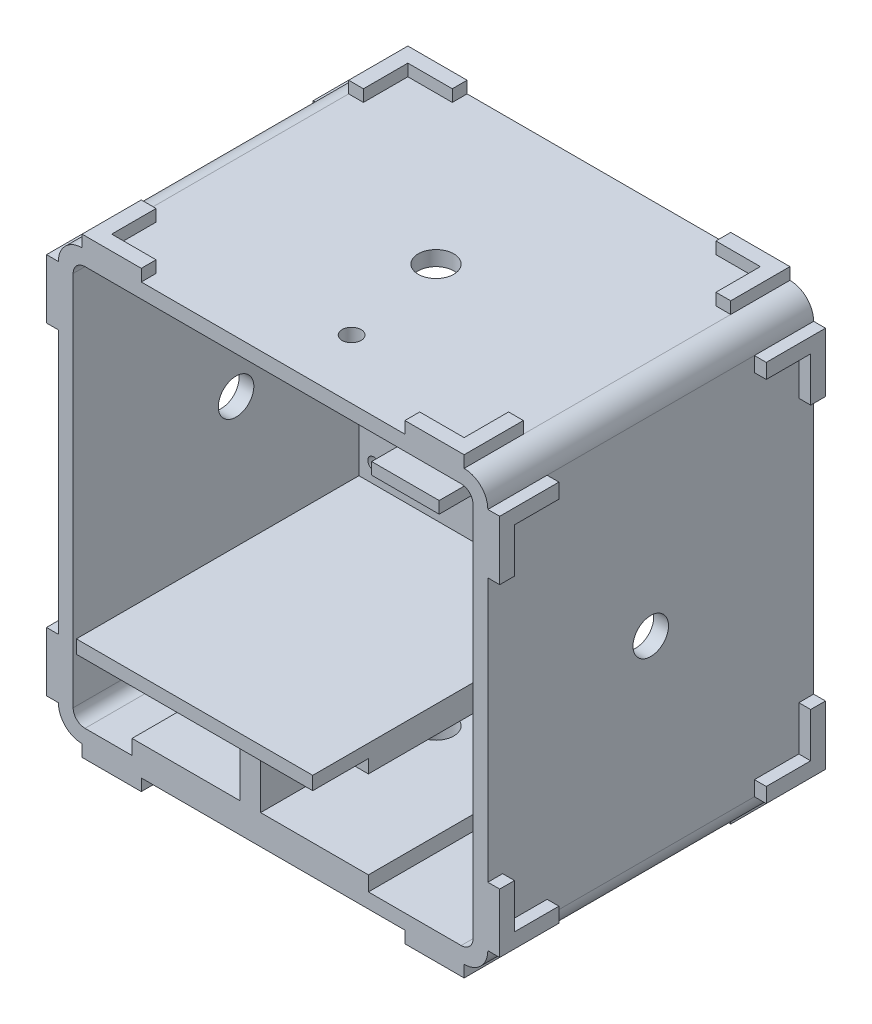
SolidWorks part; units mm, degrees
ref_plane "Front Plane" through (0, 0, 0) normal (0, 0, 1) x (1, 0, 0)
ref_plane "Top Plane" through (0, 0, 0) normal (0, 1, 0) x (1, 0, 0)
ref_plane "Right Plane" through (0, 0, 0) normal (1, 0, 0) x (0, 0, -1)
sketch "Sketch1" plane through (0, 0, 0) normal (0, 0, 1) x (1, 0, 0)
  line L0 (-33.75, -33.75) -> (33.75, -33.75) construction
  line L1 (-31.75, 33.75) -> (31.75, 33.75)
  line L2 (-33.75, 31.75) -> (-33.75, -31.75)
  line L3 (-31.75, -33.75) -> (31.75, -33.75)
  line L4 (33.75, 31.75) -> (33.75, -31.75)
  line L5 (-36.25, 32.25) -> (-36.25, -32.25)
  line L6 (33.75, 33.75) -> (33.75, -33.75) construction
  line L7 (-32.25, -36.25) -> (32.25, -36.25)
  line L8 (36.25, 32.25) -> (36.25, -32.25)
  line L9 (-32.25, 36.25) -> (32.25, 36.25)
  line L10 (-36.25, 36.25) -> (-36.25, -36.25) construction
  line L11 (-36.25, 36.25) -> (36.25, 36.25) construction
  line L12 (-33.75, 33.75) -> (33.75, 33.75) construction
  line L13 (-33.75, 33.75) -> (-33.75, -33.75) construction
  line L14 (-36.25, -36.25) -> (36.25, -36.25) construction
  line L15 (36.25, 36.25) -> (36.25, -36.25) construction
  line L16 (55, 0) -> (-55, 0) construction
  line L17 (0, -55) -> (0, 55) construction
  arc A0 (-36.25, 32.25) -> (-32.25, 36.25) centre (-32.25, 32.25) cw
  arc A1 (-31.75, 33.75) -> (-33.75, 31.75) centre (-31.75, 31.75) ccw
  arc A2 (-33.75, -31.75) -> (-31.75, -33.75) centre (-31.75, -31.75) ccw
  arc A3 (31.75, -33.75) -> (33.75, -31.75) centre (31.75, -31.75) ccw
  arc A4 (31.75, 33.75) -> (33.75, 31.75) centre (31.75, 31.75) cw
  arc A5 (-36.25, -32.25) -> (-32.25, -36.25) centre (-32.25, -32.25) ccw
  arc A6 (32.25, -36.25) -> (36.25, -32.25) centre (32.25, -32.25) ccw
  arc A7 (36.25, 32.25) -> (32.25, 36.25) centre (32.25, 32.25) ccw
  point P36 (-33.75, 0)
  point P39 (0, 33.75)
  dimension "D3" = 4
  dimension "D4" = 2
  dimension "D5" = 2
  dimension "D6" = 4
  dimension "D1" = 67.5
  dimension "D2" = 2.5
extrude "Boss-Extrude1" add sketch "Sketch1" along normal blind 55
sketch "Sketch2" plane through (0, 0, 0) normal (0, 0, 1) x (1, 0, 0)
  line L1 (-33.75, 33.75) -> (33.75, 33.75)
  line L2 (-33.75, 33.75) -> (-33.75, -33.75)
  line L3 (-33.75, -33.75) -> (33.75, -33.75)
  line L4 (33.75, 33.75) -> (33.75, -33.75)
extrude "Boss-Extrude2" add sketch "Sketch2" along normal blind 2.5
sketch "Sketch3" plane through (0, 0, 2.5) normal (0, 0, 1) x (1, 0, 0)
  line L0 (-4.38, 17.29) -> (-18.88, 12.29) construction
  line L1 (-19.88, 11.29) -> (-3.38, 11.29)
  line L2 (-18.88, 12.29) -> (-4.38, 12.29) construction
  line L3 (-18.88, 12.29) -> (-18.88, 17.29) construction
  line L4 (-18.88, 17.29) -> (-4.38, 17.29) construction
  line L5 (-4.38, 12.29) -> (-4.38, 17.29) construction
  line L6 (-3.38, 11.29) -> (-3.38, 18.29)
  line L7 (-19.88, 18.29) -> (-3.38, 18.29)
  line L8 (-19.88, 11.29) -> (-19.88, 18.29)
  line L9 (-36.25, 32.25) -> (-36.25, -32.25) construction
  line L10 (-3, -7) -> (3, -7) construction
  line L11 (-3, -7) -> (-3, 7) construction
  line L12 (-3, 7) -> (3, 7) construction
  line L13 (3, -7) -> (3, 7) construction
  line L14 (-3, -7) -> (3, 7) construction
  line L15 (-3, 7) -> (3, -7) construction
  line L16 (32.25, 36.25) -> (-32.25, 36.25) construction
  line L17 (-4, -8) -> (-4, 8)
  line L18 (-4, 8) -> (4, 8)
  line L19 (4, -8) -> (4, 8)
  line L20 (-4, -8) -> (4, -8)
  line L21 (-18.88, 17.29) -> (-4.38, 12.29) construction
  point P0 (0, 0)
  dimension "D2" = 6
  dimension "D3" = 14
  dimension "D5" = 14.5
  dimension "D6" = 5
  dimension "D7" = 16.37
  dimension "D8" = 23.96
  dimension "D1" = 1
  dimension "D4" = 1
extrude "Cut-Extrude1" cut sketch "Sketch3" against normal up to next
fillet "Fillet1" radius 1 8 edges at (-19.88, 11.29, 1.25) (-19.88, 18.29, 1.25) (-3.38, 18.29, 1.25) (-3.38, 11.29, 1.25) (4, -8, 1.25) (-4, -8, 1.25) (-4, 8, 1.25) (4, 8, 1.25)
sketch "Sketch4" plane through (0, 0, 0) normal (0, 0, -1) x (-1, 0, 0)
  line L0 (-32.25, 36.25) -> (32.25, 36.25) construction
  line L1 (-36.25, -32.25) -> (-36.25, 32.25) construction
  circle A0 centre (-28.75, 28.75) radius 1.5
  dimension "D3" = 3
  dimension "D1" = 7.5
  dimension "D2" = 7.5
extrude "Cut-Extrude2" cut sketch "Sketch4" against normal up to next
mirror "Mirror1" about plane through (0, 0, 0) normal (1, 0, 0) of "Cut-Extrude2"
mirror "Mirror2" about plane through (0, 0, 0) normal (0, 1, 0) of "Mirror1"
sketch "Sketch5" plane through (0, 0, 0) normal (1, 0, 0) x (0, 0, -1)
  line L0 (-14.7, 14) -> (-64.4, 14)
  line L1 (-16.7, 12) -> (-62.4, 12)
  line L2 (-16.7, 12) -> (-16.7, -12)
  line L3 (-16.7, -12) -> (-62.4, -12)
  line L5 (-64.4, 14) -> (-64.4, 12)
  line L6 (-14.7, -14) -> (-64.4, -14)
  line L7 (-14.7, 14) -> (-14.7, -14)
  line L8 (-62.4, 12) -> (-64.4, 12)
  line L9 (-62.4, -12) -> (-64.4, -12)
  line L10 (-64.4, -12) -> (-64.4, -14)
  line L11 (-62.4, 12) -> (-62.4, -12) construction
  line L12 (-64.4, 14) -> (-64.4, -14) construction
  line L13 (30.25, 0) -> (-30.25, 0) construction
  line L14 (-55, 32.25) -> (-55, -32.25) construction
  point P4 (0, 0)
  point P6 (0, 0)
  point P11 (0, 0)
  point P13 (0, 0)
  point P14 (0, 0)
  point P15 (0, 0)
  point P18 (0, 0)
  point P19 (-64.3967, 12)
  point P20 (0, 0)
  point P21 (-64.3967, -14)
  point P22 (-64.3967, -12)
  point P23 (-62.3967, -12)
  point P24 (-17.3967, 14)
  dimension "D1" = 45.7
  dimension "D2" = 24
  dimension "D4" = 12
  dimension "D5" = 9.4
  dimension "D3" = 2
extrude "Boss-Extrude3" add sketch "Sketch5" along normal blind 16.09 and the other way blind 23.81 separate body
sketch "Sketch6" plane through (0, 0, 64.4) normal (0, 0, 1) x (1, 0, 0)
  line L0 (-23.81, -14) -> (16.09, -14) construction
  line L1 (-23.81, -14) -> (16.09, -14)
  line L2 (-23.81, -14) -> (-23.81, -16.5)
  line L3 (-23.81, -16.5) -> (-5.61, -16.5)
  line L4 (16.09, -14) -> (16.09, -16.5)
  line L5 (-31.75, -33.75) -> (31.75, -33.75) construction
  line L6 (-23.81, -33.75) -> (16.09, -33.75)
  line L7 (-23.81, -33.75) -> (-23.81, -31.25)
  line L8 (-23.81, -31.25) -> (-5.61, -31.25)
  line L9 (16.09, -33.75) -> (16.09, -31.25)
  line L10 (-2.11, -16.5) -> (16.09, -16.5)
  line L12 (-5.61, -16.5) -> (-5.61, -31.25)
  line L14 (-2.11, -16.5) -> (-2.11, -31.25)
  line L15 (-2.11, -31.25) -> (16.09, -31.25)
  line L16 (-23.81, -12) -> (-23.81, -14) construction
  point P16 (0, 0)
  point P17 (0, 0)
  point P20 (0, 0)
  point P21 (0, 0)
  point P22 (0, 0)
  point P23 (5.59, -33.75)
  point P24 (-23.81, -33.75)
  point P25 (0, 0)
  point P26 (0, 0)
  point P27 (0, 0)
  point P28 (0, 0)
  point P29 (-23.81, -14)
  point P30 (-23.81, -16.5)
  point P31 (0, 0)
  dimension "D1" = 2.5
  dimension "D2" = 2.5
  dimension "D3" = 39.9
  dimension "D4" = 39.9
  dimension "D5" = 3.5
  dimension "D6" = 18.2
  dimension "D7" = 18.2
extrude "Boss-Extrude4" add sketch "Sketch6" against normal blind 47
sketch "Sketch7" plane through (0, 0, 64.4) normal (0, 0, 1) x (1, 0, 0)
  line L0 (-23.81, -12) -> (-23.81, -16.5) construction
  line L1 (-23.81, -14.25) -> (16.09, -14.25)
  line L2 (-23.81, -14.25) -> (-23.81, -33.75)
  line L3 (-23.81, -33.75) -> (16.09, -33.75)
  line L4 (16.09, -14.25) -> (16.09, -33.75)
  line L5 (16.09, -33.75) -> (31.75, -33.75) construction
  line L6 (16.09, -33.75) -> (16.09, -31.25) construction
extrude "Cut-Extrude3" cut sketch "Sketch7" against normal blind 9.4
sketch "Sketch8" plane through (-23.81, 0, 0) normal (-1, 0, 0) x (0, 0, 1)
  line L0 (16.7, 12) -> (16.7, -12) construction
  line L1 (16.7, 12) -> (22.2, 12)
  line L2 (16.7, 12) -> (16.7, 6.5)
  line L3 (16.7, 6.5) -> (20.6, 6.5)
  line L4 (22.2, 12) -> (22.2, 8.1)
  arc A0 (20.6, 6.5) -> (22.2, 8.1) centre (20.6, 8.1) ccw
  circle A1 centre (19.7, 9) radius 1 construction
  circle A2 centre (19.7, 9) radius 1.8
  dimension "D1" = 1.6
  dimension "D4" = 3.6
  dimension "D5" = 2
  dimension "D2" = 5.5
  dimension "D3" = 5.5
  dimension "D6" = 3
  dimension "D7" = 3
extrude "Boss-Extrude5" [suppressed] add sketch "Sketch8" against normal blind 3
sketch "Sketch9" [suppressed] plane through (-15.56, 0, 0) normal (-1, 0, 0) x (0, 0, 1)
  circle A0 centre (22.3967, 9) radius 1
  circle A1 centre (22.3967, 9) radius 2
  dimension "D1" = 2
  dimension "D2" = 1
extrude "Boss-Extrude6" [suppressed] add sketch "Sketch9" along normal blind 1.5
ref_plane "Plane1" through (-9.11, 0, 0) normal (-1, 0, 0) x (0, 0, 1)
mirror "Mirror3" [suppressed] about plane through (-9.11, 0, 0) normal (-1, 0, 0)
ref_plane "Plane2" through (0, 0, 0) normal (0, 1, 0) x (1, 0, 0)
mirror "Mirror4" [suppressed] about plane through (0, 0, 0) normal (0, 1, 0)
sketch "Sketch10" [suppressed] plane through (-36.25, 0, 0) normal (-1, 0, 0) x (0, 0, 1)
  circle A0 centre (22.3967, 9) radius 1.5
  circle A1 centre (22.3967, -9) radius 1.5
  dimension "D1" = 3
  dimension "D2" = 3
extrude "Cut-Extrude4" [suppressed] cut sketch "Sketch10" against normal through all
sketch "Sketch12" plane through (0, 36.25, 0) normal (0, 1, 0) x (1, 0, 0)
  line L0 (-32.25, -55) -> (-32.25, 0) construction
  line L1 (32.25, -55) -> (29.75, -55)
  line L2 (32.25, -55) -> (32.25, -45)
  line L3 (32.25, -45) -> (29.75, -45)
  line L4 (29.75, -52.5) -> (29.75, -45)
  line L5 (32.25, -55) -> (22.25, -55)
  line L6 (32.25, -55) -> (32.25, -52.5)
  line L7 (29.75, -52.5) -> (22.25, -52.5)
  line L8 (22.25, -55) -> (22.25, -52.5)
  line L10 (-32.25, 0) -> (-32.25, -10)
  line L11 (-32.25, -10) -> (-29.75, -10)
  line L12 (-29.75, -2.5) -> (-29.75, -10)
  line L13 (-32.25, 0) -> (-22.25, 0)
  line L15 (-29.75, -2.5) -> (-22.25, -2.5)
  line L16 (-22.25, 0) -> (-22.25, -2.5)
  line M6 (-32.25, -55) -> (32.25, -55)
  line M7 (32.25, -55) -> (32.25, 0)
  dimension "D1" = 2.5
  dimension "D2" = 10
  dimension "D3" = 2.5
  dimension "D4" = 10
  dimension "D5" = 2.5
extrude "Boss-Extrude7" add sketch "Sketch12" along normal blind 2 contours L8 L2 L3 L4 L7 M6 M7 | L10 L11 L12 L15 L16 L13 region at (31, 36.25, 54.8586)
sketch "Sketch13" plane through (0, 0, 0) normal (0, 0, -1) x (-1, 0, 0)
  line L3 (-33.75, 21.25) -> (-25.25, 21.25)
  line L4 (-21.25, 33.75) -> (-21.25, 25.25)
  line L6 (0, 35.42) -> (0, -35.42) construction
  line L8 (21.25, 33.75) -> (21.25, 25.25)
  line L9 (33.75, 21.25) -> (25.25, 21.25)
  line L12 (35.42, 0) -> (-35.42, 0) construction
  line L17 (33.75, -21.25) -> (25.25, -21.25)
  line L18 (21.25, -33.75) -> (21.25, -25.25)
  line L19 (-21.25, -33.75) -> (-21.25, -25.25)
  line L20 (-33.75, -21.25) -> (-25.25, -21.25)
  line L27 (-33.75, 21.25) -> (-33.75, -21.25)
  line L29 (33.75, 21.25) -> (33.75, -21.25)
  line L34 (-21.25, 33.75) -> (21.25, 33.75)
  line L36 (-21.25, -33.75) -> (21.25, -33.75)
  arc A2 (-25.25, 21.25) -> (-21.25, 25.25) centre (-25.25, 25.25) ccw
  arc A4 (25.25, 21.25) -> (21.25, 25.25) centre (25.25, 25.25) cw
  arc A7 (25.25, -21.25) -> (21.25, -25.25) centre (25.25, -25.25) ccw
  arc A8 (-25.25, -21.25) -> (-21.25, -25.25) centre (-25.25, -25.25) cw
  dimension "D3" = 4
extrude "Cut-Extrude6" cut sketch "Sketch13" against normal up to next and the other way through all
sketch "Sketch14" plane through (0, 0, 14.7) normal (0, 0, -1) x (-1, 0, 0)
  line L1 (23.81, 14) -> (9.11, 14)
  line L2 (23.81, 14) -> (23.81, 12)
  line L3 (23.81, 12) -> (9.11, 12)
  line L4 (9.11, 14) -> (9.11, 12)
  dimension "D1" = 14.7
  dimension "D2" = 2
extrude "Cut-Extrude7" cut sketch "Sketch14" against normal up to next
sketch "Sketch15" plane through (0, 36.25, 0) normal (0, 1, 0) x (1, 0, 0)
  line L0 (22.25, -55) -> (-32.25, -55) construction
  line L1 (33.75, -55) -> (33.75, -2.5) construction
  circle A0 centre (3.25, -45) radius 1.6
  dimension "D1" = 3.2
  dimension "D2" = 10
  dimension "D3" = 30.5
extrude "Cut-Extrude8" cut sketch "Sketch15" against normal up to surface (2.5 mm away) and the other way through all up to face at (0, 33.75, 15)
sketch "Sketch16" plane through (-33.75, 0, 0) normal (1, 0, 0) x (0, 0, -1)
  line L2 (-16, 32.15) -> (-16, 29.65)
  line L7 (-16, 29.65) -> (-8.5, 29.65)
  line L9 (-16, 32.15) -> (-8.5, 32.15)
  line L10 (-8.5, 29.65) -> (-8.5, 32.15)
  line L12 (0, -32.25) -> (0, 32.25) construction
  point P3 (-10.8312, 29.65)
  point P4 (-11.1578, 32.15)
  dimension "D1" = 7.5
  dimension "D3" = 16
extrude "Boss-Extrude8" add sketch "Sketch16" along normal blind 7
sketch "Sketch11" plane through (0, 14, 0) normal (0, 1, 0) x (1, 0, 0)
  line L0 (1.19, -39.55) -> (12.59, -39.55)
  line L1 (-23.81, -64.4) -> (1.19, -64.4)
  line L2 (-23.81, -64.4) -> (-23.81, -14.7)
  line L3 (-23.81, -14.7) -> (1.19, -14.7)
  line L4 (1.19, -39.55) -> (1.19, -14.7)
  line L5 (16.09, -64.4) -> (12.59, -64.4)
  line L6 (16.09, -64.4) -> (16.09, -14.7)
  line L7 (16.09, -14.7) -> (12.59, -14.7)
  line L8 (12.59, -39.55) -> (12.59, -14.7)
  line L9 (1.19, -64.4) -> (12.59, -64.4)
  dimension "D1" = 25
  dimension "D2" = 49.7
  dimension "D3" = 3.5
extrude "Cut-Extrude5" cut sketch "Sketch11" against normal blind 2
sketch "Sketch17" plane through (0, 0, 14.7) normal (0, 0, -1) x (-1, 0, 0)
  line L0 (-16.09, -14) -> (-16.09, 12) construction
  line L1 (-1.19, 12) -> (23.81, 12) construction
  line L2 (23.81, -14) -> (23.81, 12) construction
  circle A0 centre (-13.59, 9) radius 1
  circle A1 centre (-13.59, -9) radius 1
  circle A2 centre (21.31, -9) radius 1
  point P12 (0, 0)
  point P13 (0, 0)
  dimension "D1" = 2
  dimension "D2" = 2.5
  dimension "D3" = 3
  dimension "D4" = 2.5
  dimension "D6" = 18
extrude "Cut-Extrude9" cut sketch "Sketch17" against normal up to next
sketch "Sketch19" plane through (0, 36.25, 0) normal (0, 1, 0) x (1, 0, 0)
  line L0 (32.25, -55) -> (-32.25, 0) construction
  line L1 (-32.25, 0) -> (-22.25, 0) construction
  line L2 (32.25, 0) -> (-32.25, -55) construction
  line L3 (32.25, -45) -> (32.25, 0) construction
  line L4 (32.25, 0) -> (-22.25, 0) construction
  line L5 (-32.25, 0) -> (-32.25, -10) construction
  line L6 (-32.25, 0) -> (-32.25, -10) construction
  circle A0 centre (0, -27.5) radius 3
  point P14 (33.75, -55)
  point P15 (32.25, -55)
  point P17 (0, 0)
  point P18 (-32.25, -55)
  point P20 (0, -27.5)
  point P21 (0, 0)
  point P22 (0, 0)
  point P23 (-32.25, 0)
  dimension "D1" = 6
extrude "Cut-Extrude10" cut sketch "Sketch19" against normal blind 2.5
sketch "Sketch20" plane through (36.25, 0, -36.25) normal (-1, 0, 0) x (0, 0, 1)
  line L0 (36.25, -32.25) -> (36.25, 32.25) construction
  line L1 (36.25, -32.25) -> (36.25, -22.25)
  line L2 (36.25, -32.25) -> (46.25, -32.25)
  line L3 (46.25, -32.25) -> (46.25, -29.75)
  line L4 (38.75, -29.75) -> (46.25, -29.75)
  line L5 (36.25, -32.25) -> (36.25, -22.25)
  line L7 (38.75, -29.75) -> (38.75, -22.25)
  line L8 (36.25, -22.25) -> (38.75, -22.25)
  line L10 (91.25, 32.25) -> (81.25, 32.25)
  line L11 (81.25, 32.25) -> (81.25, 29.75)
  line L12 (88.75, 29.75) -> (81.25, 29.75)
  line L13 (91.25, 32.25) -> (91.25, 22.25)
  line L15 (88.75, 29.75) -> (88.75, 22.25)
  line L16 (91.25, 22.25) -> (88.75, 22.25)
  point P3 (0, 0)
  point P4 (91.25, 32.25)
  point P6 (36.25, -22.25)
  point P18 (88.75, 22.25)
  line M25 (36.25, -32.25) -> (36.25, 32.25)
  line M26 (36.25, 32.25) -> (91.25, 32.25)
  line M27 (91.25, 32.25) -> (91.25, -32.25)
  line M28 (91.25, -32.25) -> (36.25, -32.25)
  dimension "D1" = 2.5
  dimension "D2" = 10
  dimension "D3" = 2.5
  dimension "D4" = 10
  dimension "D5" = 2.5
  dimension "D6" = 55
  dimension "D7" = 64.5
  dimension "D8" = 10
  dimension "D9" = 7.5
  dimension "D10" = 7.5
extrude "Boss-Extrude9" add sketch "Sketch20" against normal blind 2 contours L16 L15 L12 L11 M27 M26 | L8 L7 L4 L3 M25 M28 region at (36.25, -27.25, 0.1414) region at (36.25, 32.1086, 50)
ref_axis "Axis1" through (0, 0, 67.62) along (0, 0, -1)
pattern_circular "CirPattern1" count 4 every 90 about axis through (0, 0, 67.62) along (0, 0, -1) of "Boss-Extrude7", "Cut-Extrude10"
pattern_circular "CirPattern2" count 4 every 90 about axis through (0, 0, 67.62) along (0, 0, -1) of "Boss-Extrude9"
sketch "Sketch21" plane through (0, -33.75, 0) normal (0, -1, 0) x (1, 0, 0)
  line L0 (-2.11, 25.3674) -> (-2.11, 29.6326)
  arc A0 (-2.11, 25.3674) -> (-2.11, 29.6326) centre (0, 27.5) ccw
extrude "Cut-Extrude11" cut sketch "Sketch21" against normal blind 2.5
